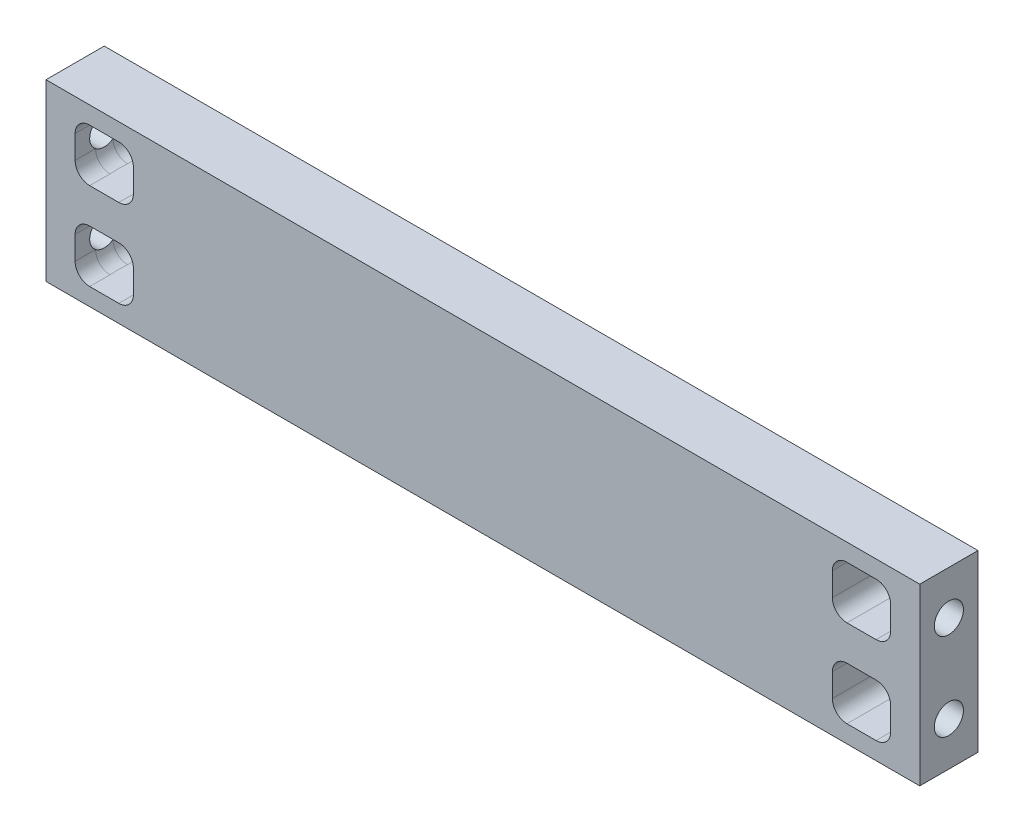
SolidWorks part; units mm, degrees
material "6061-T6 (SS)"
ref_plane "Front Plane" through (0, 0, 0) normal (0, 0, 1) x (1, 0, 0)
ref_plane "Top Plane" through (0, 0, 0) normal (0, 1, 0) x (1, 0, 0)
ref_plane "Right Plane" through (0, 0, 0) normal (1, 0, 0) x (0, 0, -1)
sketch "Sketch1" plane through (0, 0, 0) normal (0, 0, 1) x (1, 0, 0)
  line L1 (-95.25, -19.05) -> (95.25, -19.05)
  line L2 (-95.25, -19.05) -> (-95.25, 19.05)
  line L3 (-95.25, 19.05) -> (95.25, 19.05)
  line L4 (95.25, -19.05) -> (95.25, 19.05)
  line L5 (-95.25, -19.05) -> (95.25, 19.05) construction
  line L6 (-95.25, 19.05) -> (95.25, -19.05) construction
  point P0 (0, 0)
  dimension "D1" = 38.1
  dimension "D2" = 190.5
extrude "Boss-Extrude1" add sketch "Sketch1" along normal blind 12.7 contours L4 L3 L2 L1 region at (0, 0, 0)
sketch "Sketch2" plane through (0, 0, 12.7) normal (0, 0, 1) x (1, 0, 0)
  line L0 (-95.25, 19.05) -> (95.25, 19.05) construction
  line L1 (-88.9, 15.24) -> (-76.2, 15.24)
  line L2 (-88.9, 15.24) -> (-88.9, 3.81)
  line L3 (-88.9, 3.81) -> (-76.2, 3.81)
  line L4 (-76.2, 15.24) -> (-76.2, 3.81)
  line L5 (-88.9, -3.81) -> (-76.2, -3.81)
  line L6 (-88.9, -3.81) -> (-88.9, -15.24)
  line L7 (-88.9, -15.24) -> (-76.2, -15.24)
  line L8 (-76.2, -3.81) -> (-76.2, -15.24)
  line L9 (88.9, 3.81) -> (76.2, 3.81)
  line L10 (88.9, 3.81) -> (88.9, 15.24)
  line L11 (88.9, 15.24) -> (76.2, 15.24)
  line L12 (76.2, 3.81) -> (76.2, 15.24)
  line L13 (76.2, -3.81) -> (88.9, -3.81)
  line L14 (76.2, -3.81) -> (76.2, -15.24)
  line L15 (76.2, -15.24) -> (88.9, -15.24)
  line L16 (88.9, -3.81) -> (88.9, -15.24)
  line L17 (-95.25, -19.05) -> (95.25, -19.05) construction
  line L18 (-95.25, -19.05) -> (-95.25, 19.05) construction
  line L19 (95.25, -19.05) -> (95.25, 19.05) construction
  point P16 (-88.9, 9.525)
  point P17 (-88.9, -9.525)
  point P26 (88.9, 9.525)
  point P27 (88.9, -9.525)
  dimension "D1" = 11.43
  dimension "D2" = 9.525
  dimension "D3" = 9.525
  dimension "D4" = 6.35
  dimension "D5" = 6.35
  dimension "D6" = 6.35
  dimension "D7" = 6.35
  dimension "D8" = 9.525
  dimension "D9" = 9.525
  dimension "D10" = 12.7
extrude "Cut-Extrude1" cut sketch "Sketch2" against normal through all
sketch "Sketch3" plane through (-95.25, 0, 0) normal (-1, 0, 0) x (0, 0, 1)
  line L0 (12.7, 19.05) -> (0, 19.05) construction
  line L1 (12.7, -19.05) -> (12.7, 19.05) construction
  line L2 (12.7, -19.05) -> (0, -19.05) construction
  circle A0 centre (6.35, 9.525) radius 3.175
  circle A1 centre (6.35, -9.525) radius 3.175
  dimension "D1" = 6.35
  dimension "D4" = 6.35
  dimension "D2" = 9.525
  dimension "D3" = 6.35
  dimension "D5" = 6.35
  dimension "D6" = 9.525
extrude "Cut-Extrude2" cut sketch "Sketch3" against normal up to surface (6.35 mm away) up to face at (-88.9, 9.525, 6.35)
sketch "Sketch4" plane through (95.25, 0, 0) normal (1, 0, 0) x (0, 0, -1)
  circle A0 centre (-6.35, -9.525) radius 3.175 construction
  circle A1 centre (-6.35, 9.525) radius 3.175 construction
  circle A2 centre (-6.35, -9.525) radius 3.175
  circle A3 centre (-6.35, 9.525) radius 3.175
extrude "Cut-Extrude3" cut sketch "Sketch4" against normal up to surface (6.35 mm away) up to face at (88.9, 9.525, 6.35)
fillet "Fillet1" radius 3.175 16 edges at (88.9, -3.81, 6.35) (76.2, -3.81, 6.35) (76.2, -15.24, 6.35) (76.2, 3.81, 6.35) (88.9, -15.24, 6.35) (88.9, 3.81, 6.35) (88.9, 15.24, 6.35) (76.2, 15.24, 6.35) (-88.9, -15.24, 6.35) (-76.2, -15.24, 6.35) (-76.2, -3.81, 6.35) (-88.9, -3.81, 6.35) (-76.2, 3.81, 6.35) (-88.9, 3.81, 6.35) (-88.9, 15.24, 6.35) (-76.2, 15.24, 6.35)
